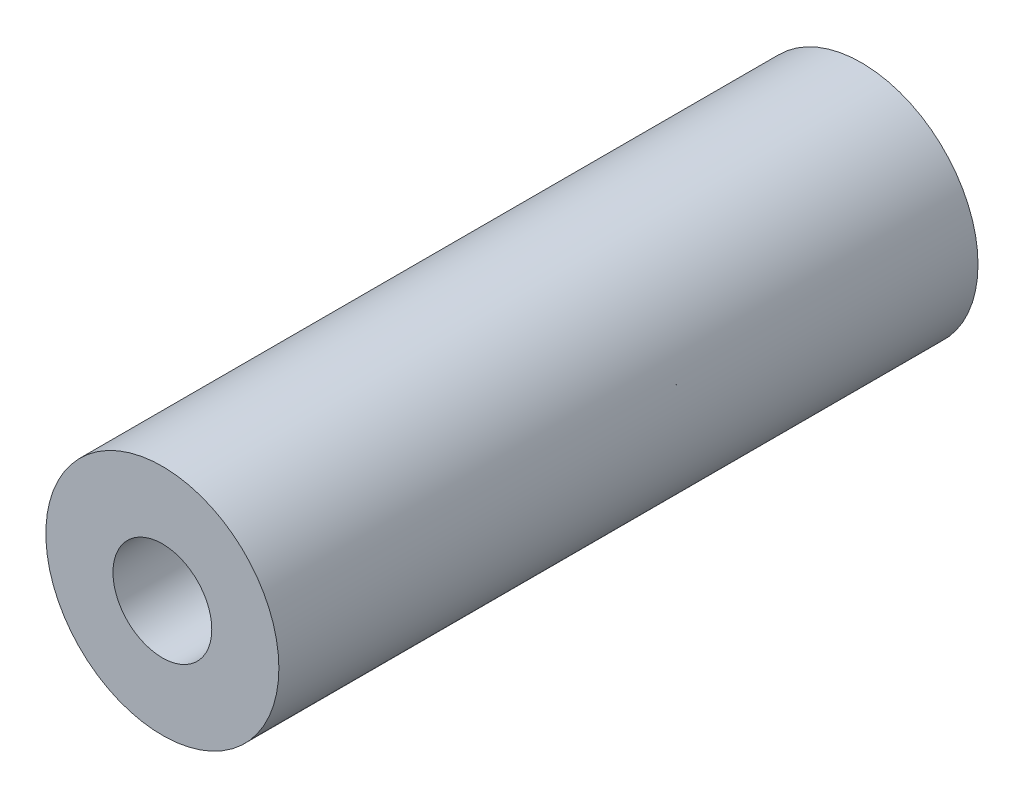
SolidWorks part; units mm, degrees
material "6061-T6 (SS)"
ref_plane "Front Plane" through (0, 0, 0) normal (0, 0, 1) x (1, 0, 0)
ref_plane "Top Plane" through (0, 0, 0) normal (0, 1, 0) x (1, 0, 0)
ref_plane "Right Plane" through (0, 0, 0) normal (1, 0, 0) x (0, 0, -1)
sketch "Sketch1" plane through (0, 0, 0) normal (0, 0, 1) x (1, 0, 0)
  circle A0 centre (0, 0) radius 4.7625
  dimension "D1" = 9.525
extrude "Boss-Extrude1" add sketch "Sketch1" along normal mid plane 28.575
hole_wizard "#10-32 Tapped Hole2" positions "3DSketch1" profile "Sketch4" tap size "#10-32" standard "ANSI Inch"
sketch3d "3DSketch1"
  line L0 (0, 0, 14.2875) -> (0, 0, -14.2875) construction
  point P0 (0, 0, 14.2875)
  point P4 (0, 0, -14.2875)
sketch "Sketch4" plane through (0, 0, 14.2875) normal (1, 0, 0) x (0, -1, 0)
  line L0 (0, 0) -> (0, 16.2908)
  line L1 (0, 16.2908) -> (2.0193, 15.0774)
  line L2 (2.0193, 15.0774) -> (2.0193, 0)
  line L5 (2.0193, 0) -> (0, 0)
  line L10 (0, 16.2908) -> (-2.0193, 15.0774) construction
  line L11 (0, -6.35) -> (0, 107.95) construction
  dimension "Tap Drill Dia." = 4.0386
  dimension "Tap Drill Depth" = 15.0774
  dimension "Drill Angle" = 118
cosmetic thread "Hole Thread2" parameters "D1"=12.7, "D2"=4.826
cosmetic thread "Hole Thread3" parameters "D1"=12.7, "D2"=4.826
